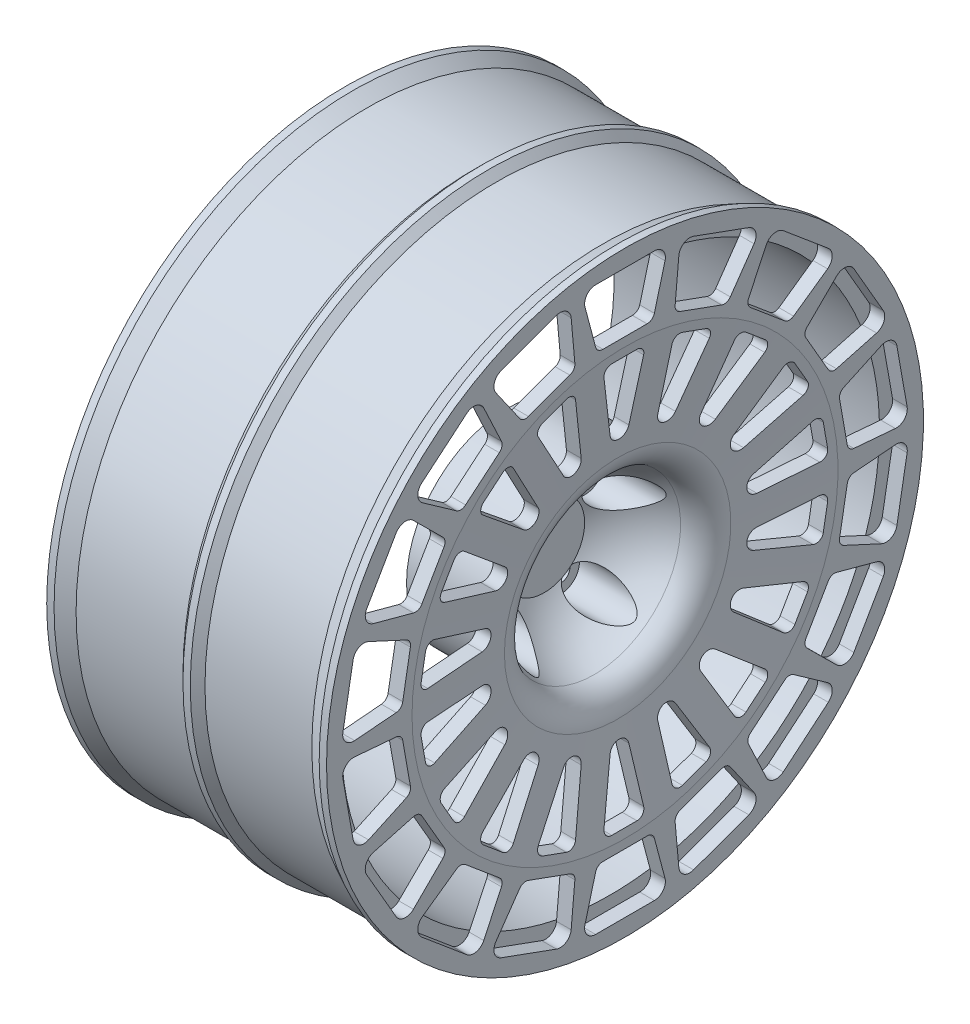
SolidWorks part; units mm, degrees
material "1060 Alloy"
ref_plane "Front Plane" through (0, 0, 0) normal (0, 0, 1) x (1, 0, 0)
ref_plane "Top Plane" through (0, 0, 0) normal (0, 1, 0) x (1, 0, 0)
ref_plane "Right Plane" through (0, 0, 0) normal (1, 0, 0) x (0, 0, -1)
sketch "Sketch1" plane through (0, 0, 0) normal (0, 0, 1) x (1, 0, 0)
  line L0 (-95.25, 0) -> (130.7804, 0) construction
  line L1 (-7.5, 198.2) -> (-80.25, 198.2)
  line L2 (-80.25, 198.2) -> (-90.25, 203.2)
  line L3 (-90.25, 203.2) -> (-95.25, 203.2)
  line L4 (-95.25, 203.2) -> (-95.25, 183.2)
  line L5 (-95.25, 183.2) -> (85.277, 183.2)
  line L6 (95.25, 183.2) -> (95.25, 203.2)
  line L7 (80.25, 198.2) -> (90.25, 203.2)
  line L8 (80.25, 198.2) -> (7.5, 198.2)
  line L9 (-2.5, 203.2) -> (2.5, 203.2)
  line L10 (2.5, 203.2) -> (7.5, 198.2)
  line L11 (-2.5, 203.2) -> (-7.5, 198.2)
  line L12 (90.25, 203.2) -> (95.25, 203.2)
  line L13 (0, -22.947) -> (0, 349.9141) construction
  line L14 (95.25, 183.2) -> (95.25, 145)
  line L15 (85.277, 183.2) -> (85.277, 145.7342)
  line L16 (85.277, 145.7342) -> (80.277, 77.8125)
  line L17 (95.25, 145) -> (90.25, 77.0783)
  line L18 (15.25, 0) -> (25.8097, 0)
  line L19 (15.25, 0) -> (15.25, 68.7378)
  line L20 (15.25, 68.7378) -> (72.25, 68.7378)
  arc A0 (74.196, 58.929) -> (25.8097, 0) centre (85.8873, 0) ccw
  arc A1 (74.196, 58.929) -> (90.25, 77.0783) centre (70.304, 78.5467) ccw
  arc A3 (72.25, 68.7378) -> (80.277, 77.8125) centre (70.304, 78.5467) ccw
  point P16 (0, 203.2)
  dimension "D10" = 57
  dimension "D11" = 20
  dimension "D1" = 406.4
  dimension "D2" = 190.5
  dimension "D3" = 58.2
  dimension "D4" = 20
  dimension "D5" = 15
  dimension "D6" = 5
  dimension "D7" = 10
  dimension "D8" = 5
  dimension "D9" = 10
  dimension "D12" = 5
  dimension "D13" = 15.25
revolve "Revolve1" add sketch "Sketch1" angle 360 about L0
sketch "Sketch2" plane through (95.25, 0, 0) normal (1, 0, 0) x (0, 0, -1)
  line L0 (-183.2, 0) -> (223.2, 0) construction
  line L1 (84.2898, 173.1081) -> (46.7021, 186.7889)
  line L2 (18.9266, 134) -> (-21.521, 134) construction
  line L3 (8.5799, 139) -> (-8.5799, 139)
  line L4 (20, 183.9972) -> (-20, 183.9972) construction
  line L5 (-13.4242, 95) -> (18.9266, 95) construction
  line L6 (20, 191.4972) -> (-20, 191.4972)
  line L7 (-15.1668, 155.9972) -> (15.1668, 155.9972) construction
  line L8 (71.71, 138.5456) -> (87.8801, 161.7756)
  line L9 (-15, 151) -> (15, 151)
  line L10 (0, 0) -> (0, 220.9303) construction
  line L11 (20, 154.7165) -> (27.2498, 182.0762)
  line L12 (-20, 154.7165) -> (-27.2498, 182.0762)
  line L13 (-13.5, 133.1099) -> (-6.3962, 93.8429)
  line L14 (13.5, 133.1099) -> (6.3962, 93.8429)
  line L15 (37.5497, 147.0239) -> (65.7404, 136.7633)
  line L16 (34.1223, 152.2264) -> (36.6673, 180.4156)
  line L17 (32.8404, 129.6997) -> (26.0857, 90.3711)
  line L18 (55.6032, 127.6828) -> (39.4784, 133.5518)
  line L19 (58.2121, 120.4651) -> (38.1066, 85.9958)
  line L20 (138.4129, 133.8396) -> (107.7711, 159.5511)
  line L21 (114.7707, 105.664) -> (137.9109, 121.9626)
  line L22 (85.5703, 125.3145) -> (108.5516, 106.0309)
  line L23 (84.129, 131.3755) -> (96.1617, 156.9943)
  line L24 (75.2198, 110.6457) -> (55.4213, 75.9992)
  line L25 (95.92, 100.9651) -> (82.7749, 111.9952)
  line L26 (95.903, 93.2905) -> (65.2208, 67.7764)
  line L27 (175.8415, 78.4281) -> (155.8415, 113.0691)
  line L28 (143.9884, 60.0377) -> (171.3075, 67.4391)
  line L29 (123.2698, 88.4904) -> (138.2698, 62.5096)
  line L30 (123.9884, 94.6788) -> (144.0577, 114.6371)
  line L31 (108.5266, 78.2463) -> (78.0722, 52.4607)
  line L32 (124.6675, 62.0696) -> (116.0876, 76.9304)
  line L33 (122.0266, 54.8636) -> (84.4684, 41.3822)
  line L34 (192.0609, 13.557) -> (185.115, 52.9493)
  line L35 (155.839, 7.1701) -> (184.0419, 4.7814)
  line L36 (146.1012, 40.993) -> (151.3107, 11.4488)
  line L37 (148.8931, 46.5624) -> (174.5781, 58.453)
  line L38 (128.7434, 36.4092) -> (91.3065, 22.5946)
  line L39 (138.3782, 15.6876) -> (135.3984, 32.5866)
  line L40 (133.4319, 9.8194) -> (93.5279, 9.9966)
  line L41 (185.115, -52.9493) -> (192.0609, -13.557)
  line L42 (148.8931, -46.5624) -> (174.5781, -58.453)
  line L43 (151.3107, -11.4488) -> (146.1012, -40.993)
  line L44 (155.839, -7.1701) -> (184.0419, -4.7814)
  line L45 (133.4319, -9.8194) -> (93.5279, -9.9966)
  line L46 (135.3984, -32.5866) -> (138.3782, -15.6876)
  line L47 (128.7434, -36.4092) -> (91.3065, -22.5946)
  line L48 (155.8415, -113.0691) -> (175.8415, -78.4281)
  line L49 (123.9884, -94.6788) -> (144.0577, -114.6371)
  line L50 (138.2698, -62.5096) -> (123.2698, -88.4904)
  line L51 (143.9884, -60.0377) -> (171.3075, -67.4391)
  line L52 (122.0266, -54.8636) -> (84.4684, -41.3822)
  line L53 (116.0876, -76.9304) -> (124.6675, -62.0696)
  line L54 (108.5266, -78.2463) -> (78.0722, -52.4607)
  line L55 (107.7711, -159.5511) -> (138.4129, -133.8396)
  line L56 (84.129, -131.3755) -> (96.1617, -156.9943)
  line L57 (108.5516, -106.0309) -> (85.5703, -125.3145)
  line L58 (114.7707, -105.664) -> (137.9109, -121.9626)
  line L59 (95.903, -93.2905) -> (65.2208, -67.7764)
  line L60 (82.7749, -111.9952) -> (95.92, -100.9651)
  line L61 (75.2198, -110.6457) -> (55.4213, -75.9992)
  line L62 (46.7021, -186.7889) -> (84.2898, -173.1081)
  line L63 (34.1223, -152.2264) -> (36.6673, -180.4156)
  line L64 (65.7404, -136.7633) -> (37.5497, -147.0239)
  line L65 (71.71, -138.5456) -> (87.8801, -161.7756)
  line L66 (58.2121, -120.4651) -> (38.1066, -85.9958)
  line L67 (39.4784, -133.5518) -> (55.6032, -127.6828)
  line L68 (32.8404, -129.6997) -> (26.0857, -90.3711)
  line L69 (-20, -191.4972) -> (20, -191.4972)
  line L70 (-20, -154.7165) -> (-27.2498, -182.0762)
  line L71 (15, -151) -> (-15, -151)
  line L72 (20, -154.7165) -> (27.2498, -182.0762)
  line L73 (13.5, -133.1099) -> (6.3962, -93.8429)
  line L74 (-8.5799, -139) -> (8.5799, -139)
  line L75 (-13.5, -133.1099) -> (-6.3962, -93.8429)
  line L76 (-84.2898, -173.1081) -> (-46.7021, -186.7889)
  line L77 (-71.71, -138.5456) -> (-87.8801, -161.7756)
  line L78 (-37.5497, -147.0239) -> (-65.7404, -136.7633)
  line L79 (-34.1223, -152.2264) -> (-36.6673, -180.4156)
  line L80 (-32.8404, -129.6997) -> (-26.0857, -90.3711)
  line L81 (-55.6032, -127.6828) -> (-39.4784, -133.5518)
  line L82 (-58.2121, -120.4651) -> (-38.1066, -85.9958)
  line L83 (-138.4129, -133.8396) -> (-107.7711, -159.5511)
  line L84 (-114.7707, -105.664) -> (-137.9109, -121.9626)
  line L85 (-85.5703, -125.3145) -> (-108.5516, -106.0309)
  line L86 (-84.129, -131.3755) -> (-96.1617, -156.9943)
  line L87 (-75.2198, -110.6457) -> (-55.4213, -75.9992)
  line L88 (-95.92, -100.9651) -> (-82.7749, -111.9952)
  line L89 (-95.903, -93.2905) -> (-65.2208, -67.7764)
  line L90 (-175.8415, -78.4281) -> (-155.8415, -113.0691)
  line L91 (-143.9884, -60.0377) -> (-171.3075, -67.4391)
  line L92 (-123.2698, -88.4904) -> (-138.2698, -62.5096)
  line L93 (-123.9884, -94.6788) -> (-144.0577, -114.6371)
  line L94 (-108.5266, -78.2463) -> (-78.0722, -52.4607)
  line L95 (-124.6675, -62.0696) -> (-116.0876, -76.9304)
  line L96 (-122.0266, -54.8636) -> (-84.4684, -41.3822)
  line L97 (-192.0609, -13.557) -> (-185.115, -52.9493)
  line L98 (-155.839, -7.1701) -> (-184.0419, -4.7814)
  line L99 (-146.1012, -40.993) -> (-151.3107, -11.4488)
  line L100 (-148.8931, -46.5624) -> (-174.5781, -58.453)
  line L101 (-128.7434, -36.4092) -> (-91.3065, -22.5946)
  line L102 (-138.3782, -15.6876) -> (-135.3984, -32.5866)
  line L103 (-133.4319, -9.8194) -> (-93.5279, -9.9966)
  line L104 (-185.115, 52.9493) -> (-192.0609, 13.557)
  line L105 (-148.8931, 46.5624) -> (-174.5781, 58.453)
  line L106 (-151.3107, 11.4488) -> (-146.1012, 40.993)
  line L107 (-155.839, 7.1701) -> (-184.0419, 4.7814)
  line L108 (-133.4319, 9.8194) -> (-93.5279, 9.9966)
  line L109 (-135.3984, 32.5866) -> (-138.3782, 15.6876)
  line L110 (-128.7434, 36.4092) -> (-91.3065, 22.5946)
  line L111 (-155.8415, 113.0691) -> (-175.8415, 78.4281)
  line L112 (-123.9884, 94.6788) -> (-144.0577, 114.6371)
  line L113 (-138.2698, 62.5096) -> (-123.2698, 88.4904)
  line L114 (-143.9884, 60.0377) -> (-171.3075, 67.4391)
  line L115 (-122.0266, 54.8636) -> (-84.4684, 41.3822)
  line L116 (-116.0876, 76.9304) -> (-124.6675, 62.0696)
  line L117 (-108.5266, 78.2463) -> (-78.0722, 52.4607)
  line L118 (-107.7711, 159.5511) -> (-138.4129, 133.8396)
  line L119 (-84.129, 131.3755) -> (-96.1617, 156.9943)
  line L120 (-108.5516, 106.0309) -> (-85.5703, 125.3145)
  line L121 (-114.7707, 105.664) -> (-137.9109, 121.9626)
  line L122 (-95.903, 93.2905) -> (-65.2208, 67.7764)
  line L123 (-82.7749, 111.9952) -> (-95.92, 100.9651)
  line L124 (-75.2198, 110.6457) -> (-55.4213, 75.9992)
  line L125 (-46.7021, 186.7889) -> (-84.2898, 173.1081)
  line L126 (-34.1223, 152.2264) -> (-36.6673, 180.4156)
  line L127 (-65.7404, 136.7633) -> (-37.5497, 147.0239)
  line L128 (-71.71, 138.5456) -> (-87.8801, 161.7756)
  line L129 (-58.2121, 120.4651) -> (-38.1066, 85.9958)
  line L130 (-39.4784, 133.5518) -> (-55.6032, 127.6828)
  line L131 (-32.8404, 129.6997) -> (-26.0857, 90.3711)
  arc A0 (-6.3962, 93.8429) -> (6.3962, 93.8429) centre (0, 95) ccw
  arc A1 (13.5, 133.1099) -> (8.5799, 139) centre (8.5799, 134) ccw
  arc A2 (-8.5799, 139) -> (-13.5, 133.1099) centre (-8.5799, 134) ccw
  arc A3 (27.2498, 182.0762) -> (20, 191.4972) centre (20, 183.9972) ccw
  arc A4 (-20, 191.4972) -> (-27.2498, 182.0762) centre (-20, 183.9972) ccw
  arc A5 (-20, 154.7165) -> (-15, 151) centre (-15.1668, 155.9972) ccw
  arc A6 (15, 151) -> (20, 154.7165) centre (15.1668, 155.9972) ccw
  arc A8 (87.8801, 161.7756) -> (84.2898, 173.1081) centre (81.7246, 166.0604) ccw
  arc A9 (46.7021, 186.7889) -> (36.6673, 180.4156) centre (44.1369, 179.7412) ccw
  arc A10 (34.1223, 152.2264) -> (37.5497, 147.0239) centre (39.1021, 151.7768) ccw
  arc A11 (39.4784, 133.5518) -> (32.8404, 129.6997) centre (37.7683, 128.8533) ccw
  arc A12 (58.2121, 120.4651) -> (55.6032, 127.6828) centre (53.8931, 122.9843) ccw
  arc A13 (26.0857, 90.3711) -> (38.1066, 85.9958) centre (32.4919, 89.2708) ccw
  arc A14 (65.7404, 136.7633) -> (71.71, 138.5456) centre (67.6063, 141.4021) ccw
  arc A15 (137.9109, 121.9626) -> (138.4129, 133.8396) centre (133.592, 128.0943) ccw
  arc A16 (107.7711, 159.5511) -> (96.1617, 156.9943) centre (102.9502, 153.8058) ccw
  arc A17 (84.129, 131.3755) -> (85.5703, 125.3145) centre (88.6546, 129.2498) ccw
  arc A18 (82.7749, 111.9952) -> (75.2198, 110.6457) centre (79.561, 108.165) ccw
  arc A19 (95.903, 93.2905) -> (95.92, 100.9651) centre (92.7061, 97.1349) ccw
  arc A20 (55.4213, 75.9992) -> (65.2208, 67.7764) centre (61.0648, 72.7742) ccw
  arc A21 (108.5516, 106.0309) -> (114.7707, 105.664) centre (111.8915, 109.7518) ccw
  arc A22 (171.3075, 67.4391) -> (175.8415, 78.4281) centre (169.3463, 74.6781) ccw
  arc A23 (155.8415, 113.0691) -> (144.0577, 114.6371) centre (149.3463, 109.3191) ccw
  arc A24 (123.9884, 94.6788) -> (123.2698, 88.4904) centre (127.5142, 91.1334) ccw
  arc A25 (116.0876, 76.9304) -> (108.5266, 78.2463) centre (111.7575, 74.4304) ccw
  arc A26 (122.0266, 54.8636) -> (124.6675, 62.0696) centre (120.3373, 59.5696) ccw
  arc A27 (78.0722, 52.4607) -> (84.4684, 41.3822) centre (82.2724, 47.5) ccw
  arc A28 (138.2698, 62.5096) -> (143.9884, 60.0377) centre (142.681, 64.8638) ccw
  arc A29 (184.0419, 4.7814) -> (192.0609, 13.557) centre (184.6748, 12.2546) ccw
  arc A30 (185.115, 52.9493) -> (174.5781, 58.453) centre (177.7289, 51.6469) ccw
  arc A31 (148.8931, 46.5624) -> (146.1012, 40.993) centre (150.9936, 42.025) ccw
  arc A32 (135.3984, 32.5866) -> (128.7434, 36.4092) centre (130.4744, 31.7184) ccw
  arc A33 (133.4319, 9.8194) -> (138.3782, 15.6876) centre (133.4541, 14.8193) ccw
  arc A34 (91.3065, 22.5946) -> (93.5279, 9.9966) centre (93.5567, 16.4966) ccw
  arc A35 (151.3107, 11.4488) -> (155.839, 7.1701) centre (156.261, 12.1522) ccw
  arc A36 (174.5781, -58.453) -> (185.115, -52.9493) centre (177.7289, -51.6469) ccw
  arc A37 (192.0609, -13.557) -> (184.0419, -4.7814) centre (184.6748, -12.2546) ccw
  arc A38 (155.839, -7.1701) -> (151.3107, -11.4488) centre (156.261, -12.1522) ccw
  arc A39 (138.3782, -15.6876) -> (133.4319, -9.8194) centre (133.4541, -14.8193) ccw
  arc A40 (128.7434, -36.4092) -> (135.3984, -32.5866) centre (130.4744, -31.7184) ccw
  arc A41 (93.5279, -9.9966) -> (91.3065, -22.5946) centre (93.5567, -16.4966) ccw
  arc A42 (146.1012, -40.993) -> (148.8931, -46.5624) centre (150.9936, -42.025) ccw
  arc A43 (144.0577, -114.6371) -> (155.8415, -113.0691) centre (149.3463, -109.3191) ccw
  arc A44 (175.8415, -78.4281) -> (171.3075, -67.4391) centre (169.3463, -74.6781) ccw
  arc A45 (143.9884, -60.0377) -> (138.2698, -62.5096) centre (142.681, -64.8638) ccw
  arc A46 (124.6675, -62.0696) -> (122.0266, -54.8636) centre (120.3373, -59.5696) ccw
  arc A47 (108.5266, -78.2463) -> (116.0876, -76.9304) centre (111.7575, -74.4304) ccw
  arc A48 (84.4684, -41.3822) -> (78.0722, -52.4607) centre (82.2724, -47.5) ccw
  arc A49 (123.2698, -88.4904) -> (123.9884, -94.6788) centre (127.5142, -91.1334) ccw
  arc A50 (96.1617, -156.9943) -> (107.7711, -159.5511) centre (102.9502, -153.8058) ccw
  arc A51 (138.4129, -133.8396) -> (137.9109, -121.9626) centre (133.592, -128.0943) ccw
  arc A52 (114.7707, -105.664) -> (108.5516, -106.0309) centre (111.8915, -109.7518) ccw
  arc A53 (95.92, -100.9651) -> (95.903, -93.2905) centre (92.7061, -97.1349) ccw
  arc A54 (75.2198, -110.6457) -> (82.7749, -111.9952) centre (79.561, -108.165) ccw
  arc A55 (65.2208, -67.7764) -> (55.4213, -75.9992) centre (61.0648, -72.7742) ccw
  arc A56 (85.5703, -125.3145) -> (84.129, -131.3755) centre (88.6546, -129.2498) ccw
  arc A57 (36.6673, -180.4156) -> (46.7021, -186.7889) centre (44.1369, -179.7412) ccw
  arc A58 (84.2898, -173.1081) -> (87.8801, -161.7756) centre (81.7246, -166.0604) ccw
  arc A59 (71.71, -138.5456) -> (65.7404, -136.7633) centre (67.6063, -141.4021) ccw
  arc A60 (55.6032, -127.6828) -> (58.2121, -120.4651) centre (53.8931, -122.9843) ccw
  arc A61 (32.8404, -129.6997) -> (39.4784, -133.5518) centre (37.7683, -128.8533) ccw
  arc A62 (38.1066, -85.9958) -> (26.0857, -90.3711) centre (32.4919, -89.2708) ccw
  arc A63 (37.5497, -147.0239) -> (34.1223, -152.2264) centre (39.1021, -151.7768) ccw
  arc A64 (-27.2498, -182.0762) -> (-20, -191.4972) centre (-20, -183.9972) ccw
  arc A65 (20, -191.4972) -> (27.2498, -182.0762) centre (20, -183.9972) ccw
  arc A66 (20, -154.7165) -> (15, -151) centre (15.1668, -155.9972) ccw
  arc A67 (8.5799, -139) -> (13.5, -133.1099) centre (8.5799, -134) ccw
  arc A68 (-13.5, -133.1099) -> (-8.5799, -139) centre (-8.5799, -134) ccw
  arc A69 (6.3962, -93.8429) -> (-6.3962, -93.8429) centre (0, -95) ccw
  arc A70 (-15, -151) -> (-20, -154.7165) centre (-15.1668, -155.9972) ccw
  arc A71 (-87.8801, -161.7756) -> (-84.2898, -173.1081) centre (-81.7246, -166.0604) ccw
  arc A72 (-46.7021, -186.7889) -> (-36.6673, -180.4156) centre (-44.1369, -179.7412) ccw
  arc A73 (-34.1223, -152.2264) -> (-37.5497, -147.0239) centre (-39.1021, -151.7768) ccw
  arc A74 (-39.4784, -133.5518) -> (-32.8404, -129.6997) centre (-37.7683, -128.8533) ccw
  arc A75 (-58.2121, -120.4651) -> (-55.6032, -127.6828) centre (-53.8931, -122.9843) ccw
  arc A76 (-26.0857, -90.3711) -> (-38.1066, -85.9958) centre (-32.4919, -89.2708) ccw
  arc A77 (-65.7404, -136.7633) -> (-71.71, -138.5456) centre (-67.6063, -141.4021) ccw
  arc A78 (-137.9109, -121.9626) -> (-138.4129, -133.8396) centre (-133.592, -128.0943) ccw
  arc A79 (-107.7711, -159.5511) -> (-96.1617, -156.9943) centre (-102.9502, -153.8058) ccw
  arc A80 (-84.129, -131.3755) -> (-85.5703, -125.3145) centre (-88.6546, -129.2498) ccw
  arc A81 (-82.7749, -111.9952) -> (-75.2198, -110.6457) centre (-79.561, -108.165) ccw
  arc A82 (-95.903, -93.2905) -> (-95.92, -100.9651) centre (-92.7061, -97.1349) ccw
  arc A83 (-55.4213, -75.9992) -> (-65.2208, -67.7764) centre (-61.0648, -72.7742) ccw
  arc A84 (-108.5516, -106.0309) -> (-114.7707, -105.664) centre (-111.8915, -109.7518) ccw
  arc A85 (-171.3075, -67.4391) -> (-175.8415, -78.4281) centre (-169.3463, -74.6781) ccw
  arc A86 (-155.8415, -113.0691) -> (-144.0577, -114.6371) centre (-149.3463, -109.3191) ccw
  arc A87 (-123.9884, -94.6788) -> (-123.2698, -88.4904) centre (-127.5142, -91.1334) ccw
  arc A88 (-116.0876, -76.9304) -> (-108.5266, -78.2463) centre (-111.7575, -74.4304) ccw
  arc A89 (-122.0266, -54.8636) -> (-124.6675, -62.0696) centre (-120.3373, -59.5696) ccw
  arc A90 (-78.0722, -52.4607) -> (-84.4684, -41.3822) centre (-82.2724, -47.5) ccw
  arc A91 (-138.2698, -62.5096) -> (-143.9884, -60.0377) centre (-142.681, -64.8638) ccw
  arc A92 (-184.0419, -4.7814) -> (-192.0609, -13.557) centre (-184.6748, -12.2546) ccw
  arc A93 (-185.115, -52.9493) -> (-174.5781, -58.453) centre (-177.7289, -51.6469) ccw
  arc A94 (-148.8931, -46.5624) -> (-146.1012, -40.993) centre (-150.9936, -42.025) ccw
  arc A95 (-135.3984, -32.5866) -> (-128.7434, -36.4092) centre (-130.4744, -31.7184) ccw
  arc A96 (-133.4319, -9.8194) -> (-138.3782, -15.6876) centre (-133.4541, -14.8193) ccw
  arc A97 (-91.3065, -22.5946) -> (-93.5279, -9.9966) centre (-93.5567, -16.4966) ccw
  arc A98 (-151.3107, -11.4488) -> (-155.839, -7.1701) centre (-156.261, -12.1522) ccw
  arc A99 (-174.5781, 58.453) -> (-185.115, 52.9493) centre (-177.7289, 51.6469) ccw
  arc A100 (-192.0609, 13.557) -> (-184.0419, 4.7814) centre (-184.6748, 12.2546) ccw
  arc A101 (-155.839, 7.1701) -> (-151.3107, 11.4488) centre (-156.261, 12.1522) ccw
  arc A102 (-138.3782, 15.6876) -> (-133.4319, 9.8194) centre (-133.4541, 14.8193) ccw
  arc A103 (-128.7434, 36.4092) -> (-135.3984, 32.5866) centre (-130.4744, 31.7184) ccw
  arc A104 (-93.5279, 9.9966) -> (-91.3065, 22.5946) centre (-93.5567, 16.4966) ccw
  arc A105 (-146.1012, 40.993) -> (-148.8931, 46.5624) centre (-150.9936, 42.025) ccw
  arc A106 (-144.0577, 114.6371) -> (-155.8415, 113.0691) centre (-149.3463, 109.3191) ccw
  arc A107 (-175.8415, 78.4281) -> (-171.3075, 67.4391) centre (-169.3463, 74.6781) ccw
  arc A108 (-143.9884, 60.0377) -> (-138.2698, 62.5096) centre (-142.681, 64.8638) ccw
  arc A109 (-124.6675, 62.0696) -> (-122.0266, 54.8636) centre (-120.3373, 59.5696) ccw
  arc A110 (-108.5266, 78.2463) -> (-116.0876, 76.9304) centre (-111.7575, 74.4304) ccw
  arc A111 (-84.4684, 41.3822) -> (-78.0722, 52.4607) centre (-82.2724, 47.5) ccw
  arc A112 (-123.2698, 88.4904) -> (-123.9884, 94.6788) centre (-127.5142, 91.1334) ccw
  arc A113 (-96.1617, 156.9943) -> (-107.7711, 159.5511) centre (-102.9502, 153.8058) ccw
  arc A114 (-138.4129, 133.8396) -> (-137.9109, 121.9626) centre (-133.592, 128.0943) ccw
  arc A115 (-114.7707, 105.664) -> (-108.5516, 106.0309) centre (-111.8915, 109.7518) ccw
  arc A116 (-95.92, 100.9651) -> (-95.903, 93.2905) centre (-92.7061, 97.1349) ccw
  arc A117 (-75.2198, 110.6457) -> (-82.7749, 111.9952) centre (-79.561, 108.165) ccw
  arc A118 (-65.2208, 67.7764) -> (-55.4213, 75.9992) centre (-61.0648, 72.7742) ccw
  arc A119 (-85.5703, 125.3145) -> (-84.129, 131.3755) centre (-88.6546, 129.2498) ccw
  arc A120 (-36.6673, 180.4156) -> (-46.7021, 186.7889) centre (-44.1369, 179.7412) ccw
  arc A121 (-84.2898, 173.1081) -> (-87.8801, 161.7756) centre (-81.7246, 166.0604) ccw
  arc A122 (-71.71, 138.5456) -> (-65.7404, 136.7633) centre (-67.6063, 141.4021) ccw
  arc A123 (-55.6032, 127.6828) -> (-58.2121, 120.4651) centre (-53.8931, 122.9843) ccw
  arc A124 (-32.8404, 129.6997) -> (-39.4784, 133.5518) centre (-37.7683, 128.8533) ccw
  arc A125 (-38.1066, 85.9958) -> (-26.0857, 90.3711) centre (-32.4919, 89.2708) ccw
  arc A126 (-37.5497, 147.0239) -> (-34.1223, 152.2264) centre (-39.1021, 151.7768) ccw
  point P13 (0, 184)
  point P15 (0, 191.4972)
  point P18 (0, 156)
  point P393 (0, 0)
  dimension "D2" = 7.5
  dimension "D3" = 39
  dimension "D6" = 5
  dimension "D7" = 6.5
  dimension "D8" = 95
  dimension "D12" = 5
  dimension "D4" = 30
  dimension "D5" = 28
  dimension "D9" = 151
  dimension "D10" = 40
  dimension "D11" = 27
  dimension "D13" = 7.5
  dimension "D14" = 7.2498
extrude "Cut-Extrude1" cut sketch "Sketch2" against normal up to surface (9.973 mm away) and the other way through all up to face at (85.277, 0, 145.7342)
sketch "Sketch7" plane through (95.25, 0, 0) normal (1, 0, 0) x (0, 0, -1)
  line L0 (13.5, 133.1099) -> (6.3962, 93.8429) construction
  line L1 (-6.3962, 93.8429) -> (-13.5, 133.1099) construction
  line L2 (13.5, 133.1099) -> (6.3962, 93.8429)
  line L3 (-6.3962, 93.8429) -> (-13.5, 133.1099)
  line L4 (-8.5799, 139) -> (8.5799, 139) construction
  line L5 (-8.5799, 139) -> (8.5799, 139)
  line L6 (58.2121, 120.4651) -> (38.1066, 85.9958)
  line L7 (26.0857, 90.3711) -> (32.8404, 129.6997)
  line L8 (39.4784, 133.5518) -> (55.6032, 127.6828)
  line L9 (95.903, 93.2905) -> (65.2208, 67.7764)
  line L10 (55.4213, 75.9992) -> (75.2198, 110.6457)
  line L11 (82.7749, 111.9952) -> (95.92, 100.9651)
  line L12 (122.0266, 54.8636) -> (84.4684, 41.3822)
  line L13 (78.0722, 52.4607) -> (108.5266, 78.2463)
  line L14 (116.0876, 76.9304) -> (124.6675, 62.0696)
  line L15 (133.4319, 9.8194) -> (93.5279, 9.9966)
  line L16 (91.3065, 22.5946) -> (128.7434, 36.4092)
  line L17 (135.3984, 32.5866) -> (138.3782, 15.6876)
  line L18 (128.7434, -36.4092) -> (91.3065, -22.5946)
  line L19 (93.5279, -9.9966) -> (133.4319, -9.8194)
  line L20 (138.3782, -15.6876) -> (135.3984, -32.5866)
  line L21 (108.5266, -78.2463) -> (78.0722, -52.4607)
  line L22 (84.4684, -41.3822) -> (122.0266, -54.8636)
  line L23 (124.6675, -62.0696) -> (116.0876, -76.9304)
  line L24 (75.2198, -110.6457) -> (55.4213, -75.9992)
  line L25 (65.2208, -67.7764) -> (95.903, -93.2905)
  line L26 (95.92, -100.9651) -> (82.7749, -111.9952)
  line L27 (32.8404, -129.6997) -> (26.0857, -90.3711)
  line L28 (38.1066, -85.9958) -> (58.2121, -120.4651)
  line L29 (55.6032, -127.6828) -> (39.4784, -133.5518)
  line L30 (-13.5, -133.1099) -> (-6.3962, -93.8429)
  line L31 (6.3962, -93.8429) -> (13.5, -133.1099)
  line L32 (8.5799, -139) -> (-8.5799, -139)
  line L33 (-58.2121, -120.4651) -> (-38.1066, -85.9958)
  line L34 (-26.0857, -90.3711) -> (-32.8404, -129.6997)
  line L35 (-39.4784, -133.5518) -> (-55.6032, -127.6828)
  line L36 (-95.903, -93.2905) -> (-65.2208, -67.7764)
  line L37 (-55.4213, -75.9992) -> (-75.2198, -110.6457)
  line L38 (-82.7749, -111.9952) -> (-95.92, -100.9651)
  line L39 (-122.0266, -54.8636) -> (-84.4684, -41.3822)
  line L40 (-78.0722, -52.4607) -> (-108.5266, -78.2463)
  line L41 (-116.0876, -76.9304) -> (-124.6675, -62.0696)
  line L42 (-133.4319, -9.8194) -> (-93.5279, -9.9966)
  line L43 (-91.3065, -22.5946) -> (-128.7434, -36.4092)
  line L44 (-135.3984, -32.5866) -> (-138.3782, -15.6876)
  line L45 (-128.7434, 36.4092) -> (-91.3065, 22.5946)
  line L46 (-93.5279, 9.9966) -> (-133.4319, 9.8194)
  line L47 (-138.3782, 15.6876) -> (-135.3984, 32.5866)
  line L48 (-108.5266, 78.2463) -> (-78.0722, 52.4607)
  line L49 (-84.4684, 41.3822) -> (-122.0266, 54.8636)
  line L50 (-124.6675, 62.0696) -> (-116.0876, 76.9304)
  line L51 (-75.2198, 110.6457) -> (-55.4213, 75.9992)
  line L52 (-65.2208, 67.7764) -> (-95.903, 93.2905)
  line L53 (-95.92, 100.9651) -> (-82.7749, 111.9952)
  line L54 (-32.8404, 129.6997) -> (-26.0857, 90.3711)
  line L55 (-38.1066, 85.9958) -> (-58.2121, 120.4651)
  line L56 (-55.6032, 127.6828) -> (-39.4784, 133.5518)
  arc A0 (-8.5799, 139) -> (-13.5, 133.1099) centre (-8.5799, 134) ccw construction
  arc A1 (13.5, 133.1099) -> (8.5799, 139) centre (8.5799, 134) ccw construction
  arc A2 (-6.3962, 93.8429) -> (6.3962, 93.8429) centre (0, 95) ccw construction
  arc A3 (-8.5799, 139) -> (-13.5, 133.1099) centre (-8.5799, 134) ccw
  arc A4 (13.5, 133.1099) -> (8.5799, 139) centre (8.5799, 134) ccw
  arc A5 (-6.3962, 93.8429) -> (6.3962, 93.8429) centre (0, 95) ccw
  arc A6 (26.0857, 90.3711) -> (38.1066, 85.9958) centre (32.4919, 89.2708) ccw
  arc A7 (39.4784, 133.5518) -> (32.8404, 129.6997) centre (37.7683, 128.8533) ccw
  arc A8 (58.2121, 120.4651) -> (55.6032, 127.6828) centre (53.8931, 122.9843) ccw
  arc A9 (55.4213, 75.9992) -> (65.2208, 67.7764) centre (61.0648, 72.7742) ccw
  arc A10 (82.7749, 111.9952) -> (75.2198, 110.6457) centre (79.561, 108.165) ccw
  arc A11 (95.903, 93.2905) -> (95.92, 100.9651) centre (92.7061, 97.1349) ccw
  arc A12 (78.0722, 52.4607) -> (84.4684, 41.3822) centre (82.2724, 47.5) ccw
  arc A13 (116.0876, 76.9304) -> (108.5266, 78.2463) centre (111.7575, 74.4304) ccw
  arc A14 (122.0266, 54.8636) -> (124.6675, 62.0696) centre (120.3373, 59.5696) ccw
  arc A15 (91.3065, 22.5946) -> (93.5279, 9.9966) centre (93.5567, 16.4966) ccw
  arc A16 (135.3984, 32.5866) -> (128.7434, 36.4092) centre (130.4744, 31.7184) ccw
  arc A17 (133.4319, 9.8194) -> (138.3782, 15.6876) centre (133.4541, 14.8193) ccw
  arc A18 (93.5279, -9.9966) -> (91.3065, -22.5946) centre (93.5567, -16.4966) ccw
  arc A19 (138.3782, -15.6876) -> (133.4319, -9.8194) centre (133.4541, -14.8193) ccw
  arc A20 (128.7434, -36.4092) -> (135.3984, -32.5866) centre (130.4744, -31.7184) ccw
  arc A21 (84.4684, -41.3822) -> (78.0722, -52.4607) centre (82.2724, -47.5) ccw
  arc A22 (124.6675, -62.0696) -> (122.0266, -54.8636) centre (120.3373, -59.5696) ccw
  arc A23 (108.5266, -78.2463) -> (116.0876, -76.9304) centre (111.7575, -74.4304) ccw
  arc A24 (65.2208, -67.7764) -> (55.4213, -75.9992) centre (61.0648, -72.7742) ccw
  arc A25 (95.92, -100.9651) -> (95.903, -93.2905) centre (92.7061, -97.1349) ccw
  arc A26 (75.2198, -110.6457) -> (82.7749, -111.9952) centre (79.561, -108.165) ccw
  arc A27 (38.1066, -85.9958) -> (26.0857, -90.3711) centre (32.4919, -89.2708) ccw
  arc A28 (55.6032, -127.6828) -> (58.2121, -120.4651) centre (53.8931, -122.9843) ccw
  arc A29 (32.8404, -129.6997) -> (39.4784, -133.5518) centre (37.7683, -128.8533) ccw
  arc A30 (6.3962, -93.8429) -> (-6.3962, -93.8429) centre (0, -95) ccw
  arc A31 (8.5799, -139) -> (13.5, -133.1099) centre (8.5799, -134) ccw
  arc A32 (-13.5, -133.1099) -> (-8.5799, -139) centre (-8.5799, -134) ccw
  arc A33 (-26.0857, -90.3711) -> (-38.1066, -85.9958) centre (-32.4919, -89.2708) ccw
  arc A34 (-39.4784, -133.5518) -> (-32.8404, -129.6997) centre (-37.7683, -128.8533) ccw
  arc A35 (-58.2121, -120.4651) -> (-55.6032, -127.6828) centre (-53.8931, -122.9843) ccw
  arc A36 (-55.4213, -75.9992) -> (-65.2208, -67.7764) centre (-61.0648, -72.7742) ccw
  arc A37 (-82.7749, -111.9952) -> (-75.2198, -110.6457) centre (-79.561, -108.165) ccw
  arc A38 (-95.903, -93.2905) -> (-95.92, -100.9651) centre (-92.7061, -97.1349) ccw
  arc A39 (-78.0722, -52.4607) -> (-84.4684, -41.3822) centre (-82.2724, -47.5) ccw
  arc A40 (-116.0876, -76.9304) -> (-108.5266, -78.2463) centre (-111.7575, -74.4304) ccw
  arc A41 (-122.0266, -54.8636) -> (-124.6675, -62.0696) centre (-120.3373, -59.5696) ccw
  arc A42 (-91.3065, -22.5946) -> (-93.5279, -9.9966) centre (-93.5567, -16.4966) ccw
  arc A43 (-135.3984, -32.5866) -> (-128.7434, -36.4092) centre (-130.4744, -31.7184) ccw
  arc A44 (-133.4319, -9.8194) -> (-138.3782, -15.6876) centre (-133.4541, -14.8193) ccw
  arc A45 (-93.5279, 9.9966) -> (-91.3065, 22.5946) centre (-93.5567, 16.4966) ccw
  arc A46 (-138.3782, 15.6876) -> (-133.4319, 9.8194) centre (-133.4541, 14.8193) ccw
  arc A47 (-128.7434, 36.4092) -> (-135.3984, 32.5866) centre (-130.4744, 31.7184) ccw
  arc A48 (-84.4684, 41.3822) -> (-78.0722, 52.4607) centre (-82.2724, 47.5) ccw
  arc A49 (-124.6675, 62.0696) -> (-122.0266, 54.8636) centre (-120.3373, 59.5696) ccw
  arc A50 (-108.5266, 78.2463) -> (-116.0876, 76.9304) centre (-111.7575, 74.4304) ccw
  arc A51 (-65.2208, 67.7764) -> (-55.4213, 75.9992) centre (-61.0648, 72.7742) ccw
  arc A52 (-95.92, 100.9651) -> (-95.903, 93.2905) centre (-92.7061, 97.1349) ccw
  arc A53 (-75.2198, 110.6457) -> (-82.7749, 111.9952) centre (-79.561, 108.165) ccw
  arc A54 (-38.1066, 85.9958) -> (-26.0857, 90.3711) centre (-32.4919, 89.2708) ccw
  arc A55 (-55.6032, 127.6828) -> (-58.2121, 120.4651) centre (-53.8931, 122.9843) ccw
  arc A56 (-32.8404, 129.6997) -> (-39.4784, 133.5518) centre (-37.7683, 128.8533) ccw
  point P166 (0, 0)
  dimension "D1" = 95
extrude "Cut-Extrude2" cut sketch "Sketch7" against normal up to next
sketch "Sketch9" plane through (85.277, 0, 0) normal (1, 0, 0) x (0, 0, -1)
  circle A0 centre (0, 0) radius 27.5
  dimension "D1" = 55
extrude "Boss-Extrude1" add sketch "Sketch9" against normal up to next
sketch "Sketch10" plane through (85.277, 0, 0) normal (1, 0, 0) x (0, 0, -1)
  circle A0 centre (0, 0) radius 27.5 construction
  circle A1 centre (0, 0) radius 27.5
extrude "Cut-Extrude3" cut sketch "Sketch10" against normal blind 45
sketch "Sketch11" plane through (85.277, 0, 0) normal (1, 0, 0) x (0, 0, -1)
  line L0 (0, 0) -> (0, 251.2039) construction
  circle A0 centre (0, 45) radius 12.5
  circle A1 centre (42.7975, 13.9058) radius 12.5
  circle A2 centre (26.4503, -36.4058) radius 12.5
  circle A3 centre (-26.4503, -36.4058) radius 12.5
  circle A4 centre (-42.7975, 13.9058) radius 12.5
  point P16 (0, 0)
  dimension "D1" = 25
  dimension "D2" = 45
  dimension "D3" = 5
extrude "Cut-Extrude5" cut sketch "Sketch11" against normal blind 60
sketch "Sketch12" plane through (25.277, 0, 0) normal (1, 0, 0) x (0, 0, -1)
  circle A0 centre (0, 45) radius 6
  circle A1 centre (42.7975, 13.9058) radius 6
  circle A2 centre (26.4503, -36.4058) radius 6
  circle A3 centre (-26.4503, -36.4058) radius 6
  circle A4 centre (-42.7975, 13.9058) radius 6
  point P14 (0, 0)
  dimension "D1" = 12
extrude "Cut-Extrude6" cut sketch "Sketch12" against normal up to next
